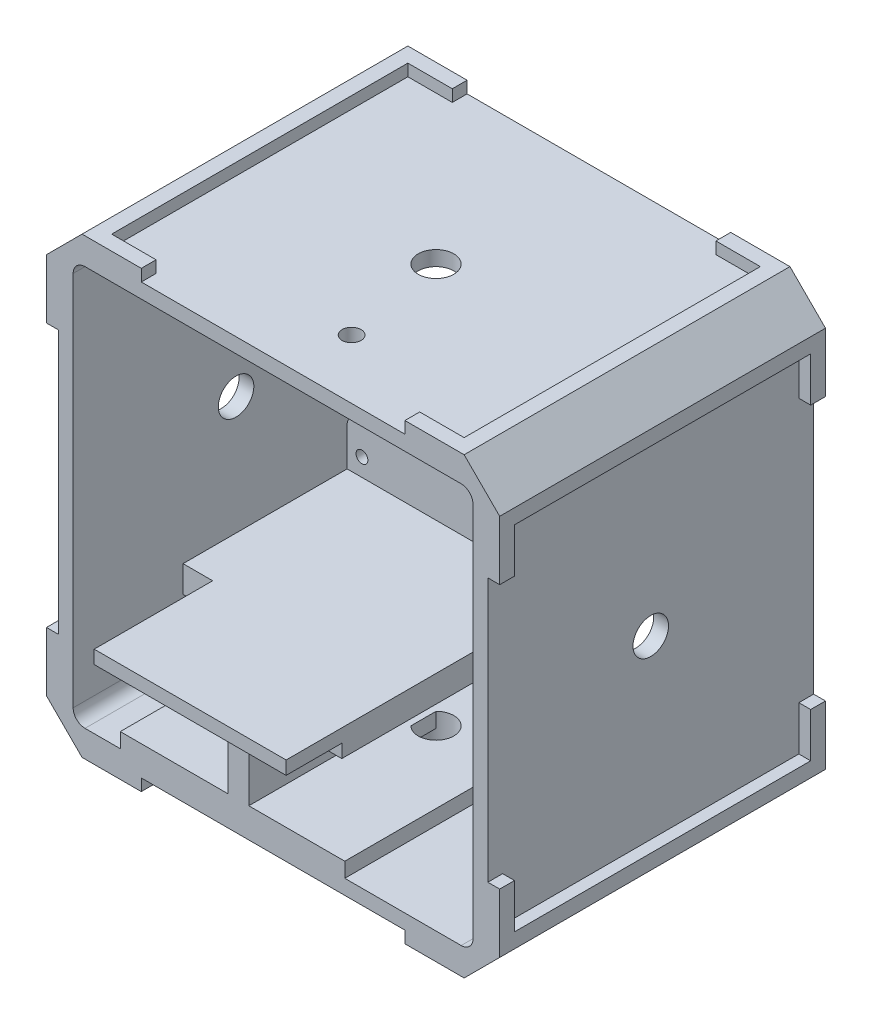
SolidWorks part; units mm, degrees
ref_plane "Front Plane" through (0, 0, 0) normal (0, 0, 1) x (1, 0, 0)
ref_plane "Top Plane" through (0, 0, 0) normal (0, 1, 0) x (1, 0, 0)
ref_plane "Right Plane" through (0, 0, 0) normal (1, 0, 0) x (0, 0, -1)
sketch "Sketch1" plane through (0, 0, 0) normal (0, 0, 1) x (1, 0, 0)
  line L0 (-33.75, -33.75) -> (33.75, -33.75) construction
  line L1 (-31.75, 33.75) -> (31.75, 33.75)
  line L2 (-33.75, 31.75) -> (-33.75, -31.75)
  line L3 (-31.75, -33.75) -> (31.75, -33.75)
  line L4 (33.75, 31.75) -> (33.75, -31.75)
  line L5 (-36.25, 32.25) -> (-36.25, -32.25)
  line L6 (33.75, 33.75) -> (33.75, -33.75) construction
  line L7 (-32.25, -36.25) -> (32.25, -36.25)
  line L8 (36.25, 32.25) -> (36.25, -32.25)
  line L9 (-32.25, 36.25) -> (32.25, 36.25)
  line L10 (-36.25, 36.25) -> (-36.25, -36.25) construction
  line L11 (-36.25, 36.25) -> (36.25, 36.25) construction
  line L12 (-33.75, 33.75) -> (33.75, 33.75) construction
  line L13 (-33.75, 33.75) -> (-33.75, -33.75) construction
  line L14 (-36.25, -36.25) -> (36.25, -36.25) construction
  line L15 (36.25, 36.25) -> (36.25, -36.25) construction
  line L16 (55, 0) -> (-55, 0) construction
  line L17 (0, -55) -> (0, 55) construction
  arc A0 (-36.25, 32.25) -> (-32.25, 36.25) centre (-32.25, 32.25) cw
  arc A1 (-31.75, 33.75) -> (-33.75, 31.75) centre (-31.75, 31.75) ccw
  arc A2 (-33.75, -31.75) -> (-31.75, -33.75) centre (-31.75, -31.75) ccw
  arc A3 (31.75, -33.75) -> (33.75, -31.75) centre (31.75, -31.75) ccw
  arc A4 (31.75, 33.75) -> (33.75, 31.75) centre (31.75, 31.75) cw
  arc A5 (-36.25, -32.25) -> (-32.25, -36.25) centre (-32.25, -32.25) ccw
  arc A6 (32.25, -36.25) -> (36.25, -32.25) centre (32.25, -32.25) ccw
  arc A7 (36.25, 32.25) -> (32.25, 36.25) centre (32.25, 32.25) ccw
  point P36 (-33.75, 0)
  point P39 (0, 33.75)
  dimension "D3" = 4
  dimension "D4" = 2
  dimension "D5" = 2
  dimension "D6" = 4
  dimension "D1" = 67.5
  dimension "D2" = 2.5
extrude "Boss-Extrude1" add sketch "Sketch1" along normal blind 55
sketch "Sketch2" plane through (0, 0, 0) normal (0, 0, 1) x (1, 0, 0)
  line L1 (-33.75, 33.75) -> (33.75, 33.75)
  line L2 (-33.75, 33.75) -> (-33.75, -33.75)
  line L3 (-33.75, -33.75) -> (33.75, -33.75)
  line L4 (33.75, 33.75) -> (33.75, -33.75)
extrude "Boss-Extrude2" add sketch "Sketch2" along normal blind 2.5
sketch "Sketch3" plane through (0, 0, 2.5) normal (0, 0, 1) x (1, 0, 0)
  line L0 (-4.38, 17.29) -> (-18.88, 12.29) construction
  line L1 (-19.88, 11.29) -> (-3.38, 11.29)
  line L2 (-18.88, 12.29) -> (-4.38, 12.29) construction
  line L3 (-18.88, 12.29) -> (-18.88, 17.29) construction
  line L4 (-18.88, 17.29) -> (-4.38, 17.29) construction
  line L5 (-4.38, 12.29) -> (-4.38, 17.29) construction
  line L6 (-3.38, 11.29) -> (-3.38, 18.29)
  line L7 (-19.88, 18.29) -> (-3.38, 18.29)
  line L8 (-19.88, 11.29) -> (-19.88, 18.29)
  line L9 (-36.25, 32.25) -> (-36.25, -32.25) construction
  line L10 (-3, -7) -> (3, -7) construction
  line L11 (-3, -7) -> (-3, 7) construction
  line L12 (-3, 7) -> (3, 7) construction
  line L13 (3, -7) -> (3, 7) construction
  line L14 (-3, -7) -> (3, 7) construction
  line L15 (-3, 7) -> (3, -7) construction
  line L16 (32.25, 36.25) -> (-32.25, 36.25) construction
  line L17 (-4, -8) -> (-4, 8)
  line L18 (-4, 8) -> (4, 8)
  line L19 (4, -8) -> (4, 8)
  line L20 (-4, -8) -> (4, -8)
  line L21 (-18.88, 17.29) -> (-4.38, 12.29) construction
  point P0 (0, 0)
  dimension "D2" = 6
  dimension "D3" = 14
  dimension "D5" = 14.5
  dimension "D6" = 5
  dimension "D7" = 16.37
  dimension "D8" = 23.96
  dimension "D1" = 1
  dimension "D4" = 1
extrude "Cut-Extrude1" cut sketch "Sketch3" against normal up to next
fillet "Fillet1" radius 1 8 edges at (-19.88, 11.29, 1.25) (-19.88, 18.29, 1.25) (-3.38, 18.29, 1.25) (-3.38, 11.29, 1.25) (4, -8, 1.25) (-4, -8, 1.25) (-4, 8, 1.25) (4, 8, 1.25)
sketch "Sketch4" plane through (0, 0, 0) normal (0, 0, -1) x (-1, 0, 0)
  line L0 (-32.25, 36.25) -> (32.25, 36.25) construction
  line L1 (-36.25, -32.25) -> (-36.25, 32.25) construction
  circle A0 centre (-28.75, 28.75) radius 1.5
  dimension "D3" = 3
  dimension "D1" = 7.5
  dimension "D2" = 7.5
extrude "Cut-Extrude2" cut sketch "Sketch4" against normal up to next
mirror "Mirror1" about plane through (0, 0, 0) normal (1, 0, 0) of "Cut-Extrude2"
mirror "Mirror2" about plane through (0, 0, 0) normal (0, 1, 0) of "Mirror1"
sketch "Sketch5" plane through (0, 0, 0) normal (1, 0, 0) x (0, 0, -1)
  line L2 (-16.7, 12) -> (-16.7, -12)
  line L3 (-16.7, -12) -> (-62.4, -12)
  line L6 (-14.7, -14) -> (-64.4, -14)
  line L7 (-14.7, 12) -> (-14.7, -14)
  line L9 (-62.4, -12) -> (-64.4, -12)
  line L10 (-64.4, -12) -> (-64.4, -14)
  line L11 (-62.4, 12) -> (-62.4, -12) construction
  line L12 (-64.4, 14) -> (-64.4, -14) construction
  line L15 (-16.7, 12) -> (-14.7, 12)
  line L16 (-14.7, 14) -> (-14.7, -14) construction
  line L17 (-14.7, 14) -> (-64.4, 14) construction
  line L18 (-16.7, 12) -> (-62.4, 12) construction
  dimension "D1" = 24
  dimension "D2" = 49.7
  dimension "D3" = 2
extrude "Boss-Extrude3" add sketch "Sketch5" along normal blind 14.6 and the other way blind 25.8 separate body
sketch "Sketch6" plane through (0, 0, 64.4) normal (0, 0, 1) x (1, 0, 0)
  line L0 (-25.8, -14) -> (14.6, -14) construction
  line L1 (-25.8, -14) -> (12.1, -14)
  line L2 (-25.8, -14) -> (-25.8, -16.5)
  line L3 (-25.8, -16.5) -> (-7.6, -16.5)
  line L4 (12.1, -14) -> (12.1, -16.5)
  line L5 (-31.75, -33.75) -> (31.75, -33.75) construction
  line L6 (-25.8, -33.75) -> (12.1, -33.75)
  line L7 (-25.8, -33.75) -> (-25.8, -31.25)
  line L8 (-25.8, -31.25) -> (-7.6, -31.25)
  line L9 (12.1, -33.75) -> (12.1, -31.25)
  line L10 (-4.1, -16.5) -> (12.1, -16.5)
  line L12 (-7.6, -16.5) -> (-7.6, -31.25)
  line L14 (-4.1, -16.5) -> (-4.1, -31.25)
  line L15 (-4.1, -31.25) -> (12.1, -31.25)
  line L16 (-25.8, -12) -> (-25.8, -14) construction
  dimension "D1" = 2.5
  dimension "D2" = 2.5
  dimension "D3" = 37.9
  dimension "D4" = 37.9
  dimension "D5" = 3.5
  dimension "D6" = 18.2
  dimension "D7" = 18.2
extrude "Boss-Extrude4" add sketch "Sketch6" against normal blind 47
sketch "Sketch7" plane through (0, 0, 64.4) normal (0, 0, 1) x (1, 0, 0)
  line L0 (-25.8, -12) -> (-25.8, -16.5) construction
  line L1 (-25.8, -14.25) -> (12.1, -14.25)
  line L2 (-25.8, -14.25) -> (-25.8, -33.75)
  line L3 (-25.8, -33.75) -> (12.1, -33.75)
  line L4 (12.1, -14.25) -> (12.1, -33.75)
  line L5 (12.1, -33.75) -> (31.75, -33.75) construction
  line L6 (12.1, -33.75) -> (12.1, -31.25) construction
extrude "Cut-Extrude3" cut sketch "Sketch7" against normal blind 9.4
sketch "Sketch9" [suppressed] plane through (-15.56, 0, 0) normal (-1, 0, 0) x (0, 0, 1)
  circle A0 centre (22.3967, 9) radius 1
  circle A1 centre (22.3967, 9) radius 2
  dimension "D1" = 2
  dimension "D2" = 1
extrude "Boss-Extrude6" [suppressed] add sketch "Sketch9" along normal blind 1.5
ref_plane "Plane1" through (-11.1, 0, 0) normal (-1, 0, 0) x (0, 0, 1)
sketch "Sketch10" [suppressed] plane through (-36.25, 0, 0) normal (-1, 0, 0) x (0, 0, 1)
  circle A0 centre (22.3967, 9) radius 1.5
  circle A1 centre (22.3967, -9) radius 1.5
  dimension "D1" = 3
  dimension "D2" = 3
extrude "Cut-Extrude4" [suppressed] cut sketch "Sketch10" against normal through all
sketch "Sketch12" plane through (0, 36.25, 0) normal (0, 1, 0) x (1, 0, 0)
  line L0 (-32.25, -55) -> (-32.25, 0) construction
  line L1 (32.25, -55) -> (29.75, -55)
  line L2 (32.25, -55) -> (32.25, -45)
  line L3 (32.25, -45) -> (29.75, -45)
  line L4 (29.75, -52.5) -> (29.75, -45)
  line L5 (32.25, -55) -> (22.25, -55)
  line L6 (32.25, -55) -> (32.25, -52.5)
  line L7 (29.75, -52.5) -> (22.25, -52.5)
  line L8 (22.25, -55) -> (22.25, -52.5)
  line L10 (-32.25, 0) -> (-32.25, -10)
  line L11 (-32.25, -10) -> (-29.75, -10)
  line L12 (-29.75, -2.5) -> (-29.75, -10)
  line L13 (-32.25, 0) -> (-22.25, 0)
  line L15 (-29.75, -2.5) -> (-22.25, -2.5)
  line L16 (-22.25, 0) -> (-22.25, -2.5)
  line M6 (-32.25, -55) -> (32.25, -55)
  line M7 (32.25, -55) -> (32.25, 0)
  dimension "D1" = 2.5
  dimension "D2" = 10
  dimension "D3" = 2.5
  dimension "D4" = 10
  dimension "D5" = 2.5
extrude "Boss-Extrude7" add sketch "Sketch12" along normal blind 2 contours L8 L2 L3 L4 L7 M6 M7 | L10 L11 L12 L15 L16 L13 region at (31, 36.25, 54.8586)
sketch "Sketch13" plane through (0, 0, 0) normal (0, 0, -1) x (-1, 0, 0)
  line L3 (-33.75, 21.25) -> (-25.25, 21.25)
  line L4 (-21.25, 33.75) -> (-21.25, 25.25)
  line L6 (0, 30.25) -> (0, -30.25) construction
  line L8 (21.25, 33.75) -> (21.25, 25.25)
  line L9 (33.75, 21.25) -> (25.25, 21.25)
  line L12 (30.25, 0) -> (-30.25, 0) construction
  line L17 (33.75, -21.25) -> (25.25, -21.25)
  line L18 (21.25, -33.75) -> (21.25, -25.25)
  line L19 (-21.25, -33.75) -> (-21.25, -25.25)
  line L20 (-33.75, -21.25) -> (-25.25, -21.25)
  line L27 (-33.75, 21.25) -> (-33.75, -21.25)
  line L29 (33.75, 21.25) -> (33.75, -21.25)
  line L34 (-21.25, 33.75) -> (21.25, 33.75)
  line L36 (-21.25, -33.75) -> (21.25, -33.75)
  arc A2 (-25.25, 21.25) -> (-21.25, 25.25) centre (-25.25, 25.25) ccw
  arc A4 (25.25, 21.25) -> (21.25, 25.25) centre (25.25, 25.25) cw
  arc A7 (25.25, -21.25) -> (21.25, -25.25) centre (25.25, -25.25) ccw
  arc A8 (-25.25, -21.25) -> (-21.25, -25.25) centre (-25.25, -25.25) cw
  dimension "D3" = 4
extrude "Cut-Extrude6" cut sketch "Sketch13" against normal up to next and the other way through all
sketch "Sketch15" plane through (0, 36.25, 0) normal (0, 1, 0) x (1, 0, 0)
  line L0 (22.25, -55) -> (-32.25, -55) construction
  line L1 (33.75, -55) -> (33.75, -2.5) construction
  circle A0 centre (3.25, -45) radius 1.6
  dimension "D1" = 3.2
  dimension "D2" = 10
  dimension "D3" = 30.5
extrude "Cut-Extrude8" cut sketch "Sketch15" against normal up to surface (2.5 mm away) and the other way through all up to face at (0, 33.75, 15)
sketch "Sketch16" plane through (-33.75, 0, 0) normal (1, 0, 0) x (0, 0, -1)
  line L2 (-16, 32.15) -> (-16, 29.65)
  line L7 (-16, 29.65) -> (-8.5, 29.65)
  line L9 (-16, 32.15) -> (-8.5, 32.15)
  line L10 (-8.5, 29.65) -> (-8.5, 32.15)
  line L12 (0, -32.25) -> (0, 32.25) construction
  dimension "D1" = 7.5
  dimension "D3" = 16
extrude "Boss-Extrude8" add sketch "Sketch16" along normal blind 7
sketch "Sketch17" plane through (0, 0, 14.7) normal (0, 0, -1) x (-1, 0, 0)
  line L0 (-14.6, -14) -> (-14.6, 12) construction
  line L2 (25.8, -14) -> (25.8, 12) construction
  line L3 (25.8, 12) -> (-14.6, 12) construction
  circle A0 centre (-12.1, 9) radius 1
  circle A1 centre (-12.1, -9) radius 1
  circle A2 centre (23.3, -9) radius 1
  dimension "D1" = 2
  dimension "D2" = 2.5
  dimension "D3" = 3
  dimension "D4" = 2.5
  dimension "D6" = 18
extrude "Cut-Extrude9" cut sketch "Sketch17" against normal up to next
sketch "Sketch19" plane through (0, 36.25, 0) normal (0, 1, 0) x (1, 0, 0)
  line L0 (32.25, -55) -> (-32.25, 0) construction
  line L1 (-32.25, 0) -> (-22.25, 0) construction
  line L2 (32.25, 0) -> (-32.25, -55) construction
  line L3 (32.25, -45) -> (32.25, 0) construction
  line L4 (32.25, 0) -> (-22.25, 0) construction
  line L5 (-32.25, 0) -> (-32.25, -10) construction
  line L6 (-32.25, 0) -> (-32.25, -10) construction
  circle A0 centre (0, -27.5) radius 3
  dimension "D1" = 6
extrude "Cut-Extrude10" cut sketch "Sketch19" against normal blind 2.5
sketch "Sketch20" plane through (36.25, 0, -36.25) normal (-1, 0, 0) x (0, 0, 1)
  line L0 (36.25, -32.25) -> (36.25, 32.25) construction
  line L1 (36.25, -32.25) -> (36.25, -22.25)
  line L2 (36.25, -32.25) -> (46.25, -32.25)
  line L3 (46.25, -32.25) -> (46.25, -29.75)
  line L4 (38.75, -29.75) -> (46.25, -29.75)
  line L5 (36.25, -32.25) -> (36.25, -22.25)
  line L7 (38.75, -29.75) -> (38.75, -22.25)
  line L8 (36.25, -22.25) -> (38.75, -22.25)
  line L10 (91.25, 32.25) -> (81.25, 32.25)
  line L11 (81.25, 32.25) -> (81.25, 29.75)
  line L12 (88.75, 29.75) -> (81.25, 29.75)
  line L13 (91.25, 32.25) -> (91.25, 22.25)
  line L15 (88.75, 29.75) -> (88.75, 22.25)
  line L16 (91.25, 22.25) -> (88.75, 22.25)
  line M25 (36.25, -32.25) -> (36.25, 32.25)
  line M26 (36.25, 32.25) -> (91.25, 32.25)
  line M27 (91.25, 32.25) -> (91.25, -32.25)
  line M28 (91.25, -32.25) -> (36.25, -32.25)
  dimension "D1" = 2.5
  dimension "D2" = 10
  dimension "D3" = 2.5
  dimension "D4" = 10
  dimension "D5" = 2.5
  dimension "D6" = 55
  dimension "D7" = 64.5
  dimension "D8" = 10
  dimension "D9" = 7.5
  dimension "D10" = 7.5
extrude "Boss-Extrude9" add sketch "Sketch20" against normal blind 2 contours L16 L15 L12 L11 M27 M26 | L8 L7 L4 L3 M25 M28 region at (36.25, -27.25, 0.1414) region at (36.25, 32.1086, 50)
ref_axis "Axis1" through (0, 0, 67.62) along (0, 0, -1)
pattern_circular "CirPattern1" count 4 every 90 about axis through (0, 0, 67.62) along (0, 0, -1) of "Boss-Extrude7", "Cut-Extrude10"
pattern_circular "CirPattern2" count 4 every 90 about axis through (0, 0, 67.62) along (0, 0, -1) of "Boss-Extrude9"
sketch "Sketch21" plane through (0, -33.75, 0) normal (0, -1, 0) x (1, 0, 0)
  line L0 (-2.11, 25.3674) -> (-2.11, 29.6326)
  arc A0 (-2.11, 25.3674) -> (-2.11, 29.6326) centre (0, 27.5) ccw
extrude "Cut-Extrude11" cut sketch "Sketch21" against normal blind 2.5
sketch "Sketch22" plane through (0, 0, 55) normal (0, 0, 1) x (1, 0, 0)
  line L0 (-38.25, 32.25) -> (-32.25, 38.25)
  line L1 (-32.25, 38.25) -> (-29.75, 38.25)
  line L8 (-29.75, 38.25) -> (-29.75, 33.75)
  line L13 (-38.25, 29.75) -> (-33.75, 29.75)
  line L20 (-38.25, 29.75) -> (-38.25, 32.25)
  line L24 (-32.25, 38.25) -> (-22.25, 38.25) construction
  line L26 (-33.75, 31.75) -> (-33.75, -31.75) construction
  line L27 (-38.25, 22.25) -> (-38.25, 32.25) construction
  line L28 (0, -30.25) -> (0, 30.25) construction
  line L29 (33.75, 33.75) -> (33.75, 29.75)
  line L30 (33.75, 33.75) -> (29.75, 33.75)
  line L31 (38.25, 29.75) -> (38.25, 32.25)
  line L32 (38.25, 29.75) -> (33.75, 29.75)
  line L33 (-33.75, 33.75) -> (-29.75, 33.75)
  line L34 (-33.75, 33.75) -> (-33.75, 29.75)
  line L37 (29.75, 38.25) -> (29.75, 33.75)
  line L38 (32.25, 38.25) -> (29.75, 38.25)
  line L39 (38.25, 32.25) -> (32.25, 38.25)
  line L40 (30.25, 0) -> (-30.25, 0) construction
  line L41 (38.25, -32.25) -> (32.25, -38.25)
  line L42 (32.25, -38.25) -> (29.75, -38.25)
  line L43 (29.75, -38.25) -> (29.75, -33.75)
  line L44 (-33.75, -33.75) -> (-33.75, -29.75)
  line L45 (-33.75, -33.75) -> (-29.75, -33.75)
  line L46 (38.25, -29.75) -> (33.75, -29.75)
  line L47 (38.25, -29.75) -> (38.25, -32.25)
  line L48 (33.75, -33.75) -> (29.75, -33.75)
  line L49 (33.75, -33.75) -> (33.75, -29.75)
  line L50 (-38.25, -29.75) -> (-38.25, -32.25)
  line L51 (-38.25, -29.75) -> (-33.75, -29.75)
  line L52 (-29.75, -38.25) -> (-29.75, -33.75)
  line L53 (-32.25, -38.25) -> (-29.75, -38.25)
  line L54 (-38.25, -32.25) -> (-32.25, -38.25)
  dimension "D1" = 2.5
  dimension "D2" = 2.5
extrude "Boss-Extrude12" add sketch "Sketch22" against normal through all
sketch "Sketch23" plane through (0, 0, 14.7) normal (0, 0, -1) x (-1, 0, 0)
  line L0 (25.8, 12) -> (-14.6, 12) construction
  line L1 (19.3, 12) -> (25.8, 12)
  line L2 (19.3, 12) -> (19.3, -4)
  line L3 (19.3, -4) -> (25.8, -4)
  line L4 (25.8, 12) -> (25.8, -4)
  line L5 (25.8, -14) -> (25.8, 12) construction
  circle A0 centre (23.3, -9) radius 1 construction
  dimension "D1" = 5
  dimension "D2" = 6.5
extrude "Cut-Extrude12" cut sketch "Sketch23" against normal up to next
sketch "Sketch24" plane through (14.6, 0, 0) normal (1, 0, 0) x (0, 0, -1)
  line L0 (-14.7, -14) -> (-14.7, 12) construction
  line L1 (-17.4, -16.5) -> (-17.4, -13.792)
  line L2 (-17.4, -13.792) -> (-14.7, -14)
  arc A0 (-14.7, -14) -> (-17.4, -16.5) centre (-17.4, -13.792) cw
  point P3 (0, 0)
extrude "Boss-Extrude13" add sketch "Sketch24" against normal up to surface (40.4 mm away) up to face at (-25.8, -12.15, 33.64)
fillet "Fillet2" radius 1.5 1 edges at (14.6, 12, 15.7)
chamfer "Chamfer1" distance 0.5 angle 45 2 edges at (-26.75, 32.15, 12.25) (-30.2298, 32.15, 16)
sketch "Sketch25" plane through (0, -12, 0) normal (0, 1, 0) x (1, 0, 0)
  line L1 (14.6, -64.4) -> (11.6, -64.4)
  line L2 (14.6, -64.4) -> (14.6, -29.4)
  line L3 (14.6, -29.4) -> (11.6, -29.4)
  line L4 (11.6, -64.4) -> (11.6, -29.4)
  line L5 (-25.8, -64.4) -> (-20.8, -64.4)
  line L6 (-25.8, -64.4) -> (-25.8, -44.4)
  line L7 (-25.8, -44.4) -> (-20.8, -44.4)
  line L8 (-20.8, -64.4) -> (-20.8, -44.4)
  dimension "D1" = 3
  dimension "D2" = 35
  dimension "D3" = 5
  dimension "D4" = 20
extrude "Cut-Extrude13" cut sketch "Sketch25" against normal up to next
fillet "Fillet3" radius 1.5 3 edges at (-19.3, 12, 15.7) (-19.3, -4, 15.7) (-25.8, -4, 15.7)
